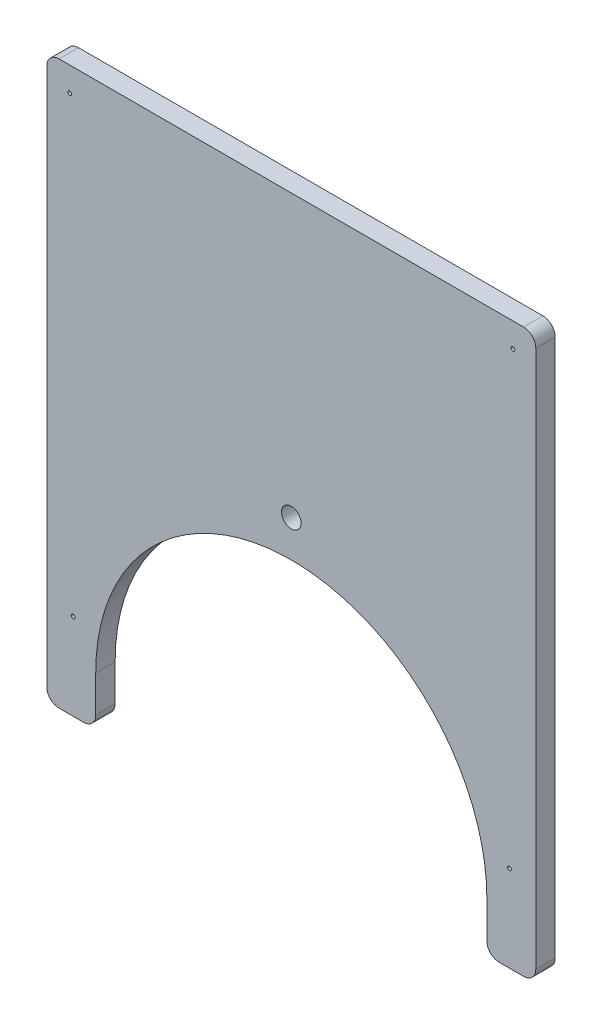
SolidWorks part; units mm, degrees
ref_plane "Front Plane" through (0, 0, 0) normal (0, 0, 1) x (1, 0, 0)
ref_plane "Top Plane" through (0, 0, 0) normal (0, 1, 0) x (1, 0, 0)
ref_plane "Right Plane" through (0, 0, 0) normal (1, 0, 0) x (0, 0, -1)
sketch "Sketch1" plane through (0, 0, 0) normal (0, 0, 1) x (1, 0, 0)
  line L1 (-200, 230) -> (200, 230)
  line L2 (-200, 230) -> (-200, -230)
  line L3 (-200, -230) -> (200, -230)
  line L4 (200, 230) -> (200, -230)
  line L5 (-200, 230) -> (200, -230) construction
  line L6 (-200, -230) -> (200, 230) construction
  point P0 (0, 0)
  dimension "D1" = 400
  dimension "D2" = 460
extrude "Boss-Extrude1" add sketch "Sketch1" against normal blind 15.875
sketch "Sketch2" plane through (0, 0, 0) normal (0, 0, 1) x (1, 0, 0)
  line L0 (160, -230) -> (160, -190)
  line L1 (-200, -230) -> (200, -230) construction
  line L2 (-160, -230) -> (-160, -190)
  line L3 (-160, -230) -> (160, -230)
  line L4 (200, -230) -> (200, 230) construction
  arc A0 (160, -190) -> (-160, -190) centre (0, -190) ccw
  dimension "D2" = 40
  dimension "D1" = 40
extrude "Cut-Extrude1" cut sketch "Sketch2" against normal through all
fillet "Fillet1" radius 10 6 edges at (-160, -230, -7.9375) (-200, -230, -7.9375) (160, -230, -7.9375) (200, -230, -7.9375) (-200, 230, -7.9375) (200, 230, -7.9375)
sketch "Sketch3" plane through (0, 0, 0) normal (0, 0, 1) x (1, 0, 0)
  line L0 (190, 230) -> (-190, 230) construction
  circle A0 centre (0, 0) radius 8
  dimension "D2" = 16
  dimension "D1" = 230
extrude "Cut-Extrude2" cut sketch "Sketch3" against normal through all
sketch "Sketch4" plane through (0, 0, 0) normal (0, 0, 1) x (1, 0, 0)
  point P0 (181.2487, 210.112)
  point P1 (-181.2487, 210.112)
  point P3 (-178.461, -159.2706)
  point P5 (178.461, -159.2706)
sketch "Sketch5" plane through (0, 0, 0) normal (0, 0, 1) x (1, 0, 0)
  line L0 (-200, 220) -> (-200, -220) construction
  line L1 (190, 230) -> (-190, 230) construction
  circle A1 centre (-181.2487, 210.112) radius 1.5875
  circle A3 centre (-178.461, -159.2706) radius 1.5875
  dimension "D5" = 3.175
  dimension "D1" = 21.539
  dimension "D2" = 389.2706
  dimension "D3" = 18.7513
  dimension "D4" = 19.888
extrude "Cut-Extrude3" cut sketch "Sketch5" against normal through all
mirror "Mirror1" about plane through (0, 0, 0) normal (1, 0, 0) of "Cut-Extrude3"
